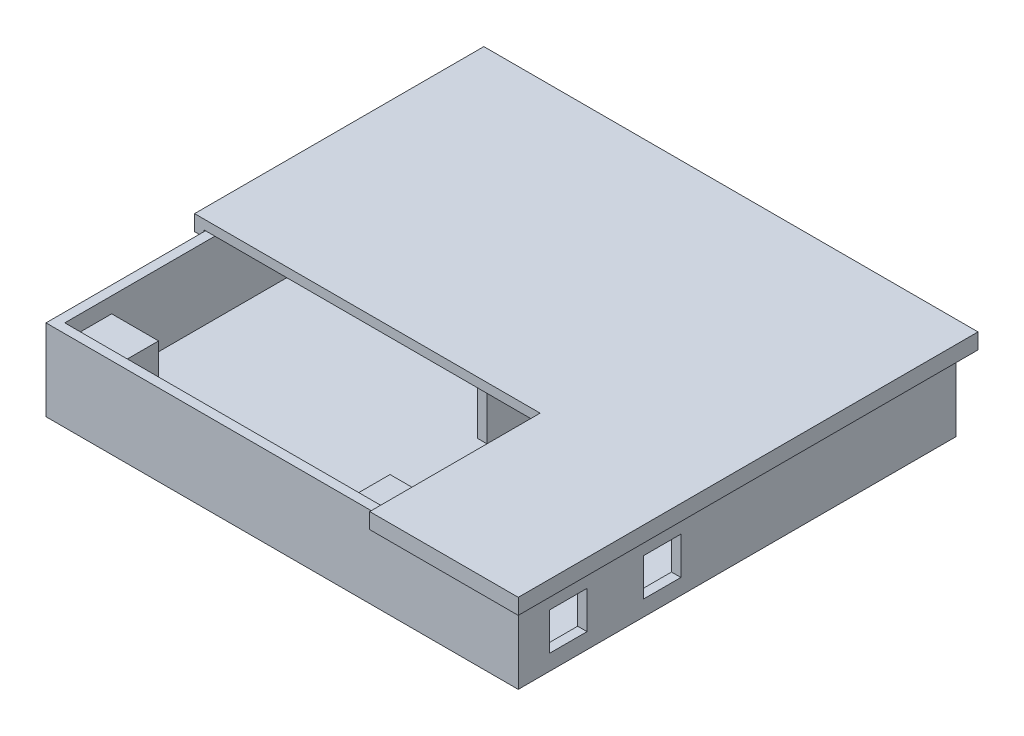
SolidWorks part; units mm, degrees
ref_plane "Front Plane" through (0, 0, 0) normal (0, 0, 1) x (1, 0, 0)
ref_plane "Top Plane" through (0, 0, 0) normal (0, 1, 0) x (1, 0, 0)
ref_plane "Right Plane" through (0, 0, 0) normal (1, 0, 0) x (0, 0, -1)
sketch "Sketch2" plane through (0, 0, 0) normal (0, 1, 0) x (1, 0, 0)
  line L1 (-75.5, -70) -> (75.5, -70)
  line L2 (-75.5, -70) -> (-75.5, 70)
  line L3 (-75.5, 70) -> (75.5, 70)
  line L4 (75.5, -70) -> (75.5, 70)
  line L5 (-75.5, -70) -> (75.5, 70) construction
  line L6 (-75.5, 70) -> (75.5, -70) construction
  line L7 (-72.5, -67) -> (72.5, -67)
  line L8 (-72.5, -67) -> (-72.5, 67)
  line L9 (-72.5, 67) -> (72.5, 67)
  line L10 (72.5, -67) -> (72.5, 67)
  line L11 (-72.5, -67) -> (72.5, 67) construction
  line L12 (-72.5, 67) -> (72.5, -67) construction
  point P0 (0, 0)
  point P6 (0, 0)
  dimension "D1" = 3
  dimension "D2" = 3
  dimension "D3" = 145
  dimension "D4" = 134
extrude "Boss-Extrude1" add sketch "Sketch2" along normal blind 26
extrude "Boss-Extrude2" add sketch "Sketch2<2>" along normal blind 3 contours L7 L10 L9 L8 region at (0, 0, 0)
sketch "Sketch2<2>" plane through (0, 0, 0) normal (0, 1, 0) x (1, 0, 0) same geometry as "Sketch2"
sketch "Sketch3" plane through (0, 26, 0) normal (0, 1, 0) x (1, 0, 0)
  line L0 (75.5, 70) -> (-75.5, 70) construction
  line L1 (-72.5, 67) -> (-55.5, 67)
  line L2 (-72.5, 67) -> (-72.5, 70)
  line L3 (-72.5, 70) -> (-55.5, 70)
  line L4 (-55.5, 67) -> (-55.5, 70)
  line L5 (72.5, -67) -> (72.5, 67) construction
  line L6 (-55.5, 67) -> (72.5, 67)
  line L7 (-55.5, 67) -> (-55.5, 70)
  line L8 (-55.5, 70) -> (72.5, 70)
  line L9 (72.5, 67) -> (72.5, 70)
  line M3 (75.5, 70) -> (-75.5, 70)
  line M9 (-72.5, 67) -> (72.5, 67)
  dimension "D1" = 17
extrude "Cut-Extrude1" cut sketch "Sketch3" against normal blind 23 contours L9 L4 M9 M3 region at (8.5, 26, -68.5)
sketch "Sketch4" plane through (75.5, 0, 0) normal (1, 0, 0) x (0, 0, -1)
  line L0 (-70, 0) -> (70, 0) construction
  line L1 (-60, 5) -> (-48, 5)
  line L2 (-60, 5) -> (-60, 17)
  line L3 (-60, 17) -> (-48, 17)
  line L4 (-48, 5) -> (-48, 17)
  line L5 (-30, 5) -> (-18, 5)
  line L6 (-30, 5) -> (-30, 17)
  line L7 (-30, 17) -> (-18, 17)
  line L8 (-18, 5) -> (-18, 17)
  line L9 (-70, 26) -> (-70, 0) construction
  dimension "D1" = 12
  dimension "D2" = 12
  dimension "D3" = 12
  dimension "D4" = 12
  dimension "D5" = 30
  dimension "D6" = 5
  dimension "D7" = 10
extrude "Cut-Extrude2" cut sketch "Sketch4" against normal blind 23
sketch "Sketch5" plane through (0, 3, 0) normal (0, 1, 0) x (1, 0, 0)
  line L0 (72.5, 70) -> (-55.5, 70) construction
  line L1 (2.5, 70) -> (5.5, 70)
  line L2 (2.5, 70) -> (2.5, -10)
  line L3 (2.5, -10) -> (5.5, -10)
  line L4 (5.5, 70) -> (5.5, -10)
  line L5 (-72.5, 67) -> (-72.5, -67) construction
  line L6 (5.5, 25) -> (40.5, 25)
  line L7 (5.5, 25) -> (5.5, 22)
  line L8 (5.5, 22) -> (40.5, 22)
  line L9 (40.5, 25) -> (40.5, 22)
  line M7 (72.5, 70) -> (-55.5, 70)
  dimension "D1" = 3
  dimension "D2" = 3
  dimension "D3" = 75
  dimension "D4" = 45
  dimension "D5" = 80
  dimension "D6" = 35
extrude "Boss-Extrude3" add sketch "Sketch5" along normal blind 15 contours L4 L2 L3 M7 | L9 L6 L4 L8 region at (4, 3, -30) region at (23, 3, -23.5)
sketch "Sketch6" plane through (0, 3, 0) normal (0, 1, 0) x (1, 0, 0)
  line L0 (-72.5, -67) -> (72.5, -67) construction
  line L1 (-72.5, -67) -> (-57.5, -67)
  line L2 (-72.5, -67) -> (-72.5, -52)
  line L3 (-72.5, -52) -> (-57.5, -52)
  line L4 (-57.5, -67) -> (-57.5, -52)
  line L5 (16.5, -67) -> (31.5, -67)
  line L6 (16.5, -67) -> (16.5, -52)
  line L7 (16.5, -52) -> (31.5, -52)
  line L8 (31.5, -67) -> (31.5, -52)
  line L9 (-72.5, -67) -> (-72.5, 67) construction
  dimension "D1" = 15
  dimension "D2" = 15
  dimension "D3" = 15
  dimension "D4" = 15
  dimension "D5" = 89
extrude "Boss-Extrude4" add sketch "Sketch6" along normal blind 18
sketch "Sketch7" plane through (0, 26, 0) normal (0, 1, 0) x (1, 0, 0)
  line L0 (-75.5, 70) -> (-75.5, -70) construction
  line L1 (-79, 73.5) -> (79, 73.5)
  line L2 (-79, 73.5) -> (-79, -19)
  line L3 (-79, -19) -> (79, -19)
  line L4 (79, 73.5) -> (79, -19)
  line L5 (79, -19) -> (31.5, -19)
  line L6 (79, -19) -> (79, -73.5)
  line L7 (79, -73.5) -> (31.5, -73.5)
  line L8 (31.5, -19) -> (31.5, -73.5)
  line L9 (72.5, 70) -> (5.5, 70) construction
  line L10 (75.5, -70) -> (75.5, 70) construction
  line L11 (-75.5, -70) -> (75.5, -70) construction
  line L12 (31.5, -67) -> (31.5, -52) construction
  line L13 (-57.5, -67) -> (16.5, -67) construction
  point P19 (0, 0)
  line M9 (-55.5, 67) -> (-55.5, 70)
  line M10 (-55.5, 70) -> (-75.5, 70)
  line M11 (-75.5, 70) -> (-75.5, -70)
  line M12 (-75.5, -70) -> (75.5, -70)
  line M13 (75.5, -70) -> (75.5, 70)
  line M14 (75.5, 70) -> (72.5, 70)
  line M15 (72.5, 70) -> (72.5, -67)
  line M16 (72.5, -67) -> (-72.5, -67)
  line M17 (-72.5, -67) -> (-72.5, 67)
  line M18 (-72.5, 67) -> (-55.5, 67)
  dimension "D1" = 3.5
  dimension "D2" = 3.5
  dimension "D3" = 3.5
  dimension "D4" = 3.5
  dimension "D5" = 0
  dimension "D6" = 48
extrude "Boss-Extrude5" add sketch "Sketch7" along normal blind 3 separate body contours L4 L1 L2 L3 M11 M10 M9 M18 M17 M15 M14 M13 | L3 L8 M16 M15 | L8 L7 L6 L3 M12 M13 | L3 M11 M17 M18 M9 M10 | L3 M15 M13 M14 | L8 L3 M16 M12 M13 M15 region at (0.2326, 26, -27.1667) region at (78.2771, 26, 46.25) region at (-74.5878, 26, -25.5) region at (74.8264, 26, 44.5) region at (74, 26, -25.5) region at (52, 26, 43)
sketch "Sketch8" plane through (0, 26, 0) normal (0, -1, 0) x (1, 0, 0)
  line L0 (-79, -73.5) -> (79, -73.5) construction
  line L1 (-79, 19) -> (-76, 19)
  line L2 (-79, 19) -> (-79, -73.5)
  line L3 (-79, -73.5) -> (-76, -73.5)
  line L4 (-76, 19) -> (-76, -73.5)
  line L5 (79, -73.5) -> (79, 73.5) construction
  line L6 (-76, -73.5) -> (79, -73.5)
  line L7 (-76, -73.5) -> (-76, -70.5)
  line L8 (-76, -70.5) -> (79, -70.5)
  line L9 (79, -73.5) -> (79, -70.5)
  line L10 (79, 73.5) -> (31.5, 73.5) construction
  line L11 (79, -70.5) -> (76, -70.5)
  line L12 (79, -70.5) -> (79, 73.5)
  line L13 (79, 73.5) -> (76, 73.5)
  line L14 (76, -70.5) -> (76, 73.5)
  line L15 (-76, -73.5) -> (79, -73.5)
  line L16 (31.5, 73.5) -> (76, 73.5)
  line L17 (31.5, 73.5) -> (31.5, 70.5)
  line L18 (31.5, 70.5) -> (76, 70.5)
  line L19 (76, 73.5) -> (76, 70.5)
  line M12 (79, -73.5) -> (79, 73.5)
  line M13 (79, 73.5) -> (31.5, 73.5)
  line M14 (31.5, 73.5) -> (31.5, 19)
  dimension "D1" = 3
  dimension "D2" = 3
  dimension "D3" = 3
  dimension "D4" = 3
extrude "Boss-Extrude6" add sketch "Sketch8" along normal blind 2 contours L14 L8 M12 M13 | L18 L14 M14 M13 | L3 L2 L1 L4 region at (77.5, 26, 1.5) region at (53.75, 26, 72)
sketch "Sketch9" plane through (0, 26, 0) normal (0, -1, 0) x (-1, 0, 0)
  line L1 (76, 73.5) -> (-79, 73.5)
  line L2 (76, 73.5) -> (76, 70.5)
  line L3 (76, 70.5) -> (-79, 70.5)
  line L4 (-79, 73.5) -> (-79, 70.5)
extrude "Boss-Extrude7" add sketch "Sketch9" along normal blind 2
